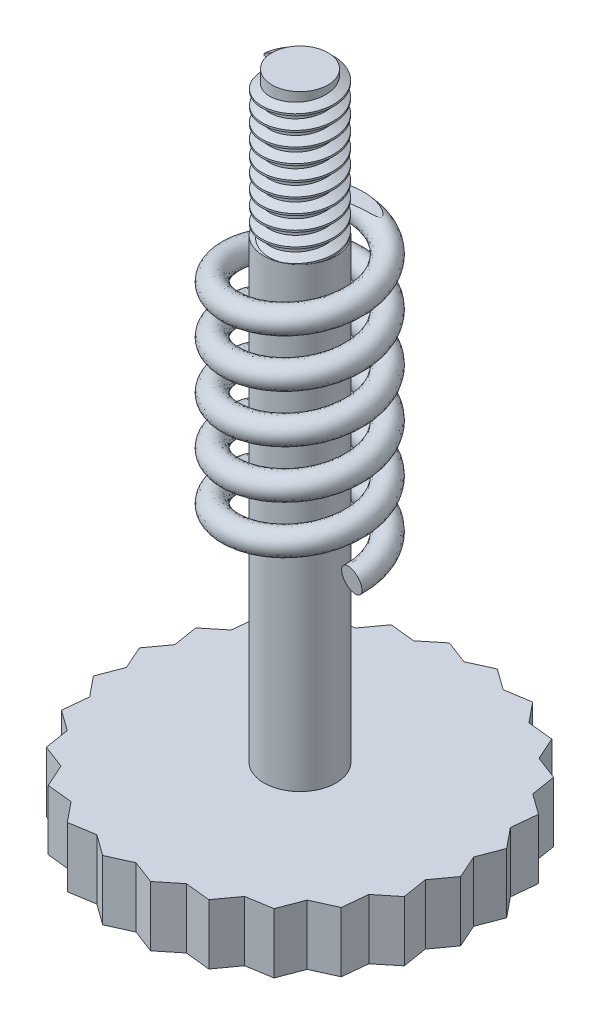
SolidWorks part; units mm, degrees
ref_plane "Front Plane" through (0, 0, 0) normal (0, 0, 1) x (1, 0, 0)
ref_plane "Top Plane" through (0, 0, 0) normal (0, 1, 0) x (1, 0, 0)
ref_plane "Right Plane" through (0, 0, 0) normal (1, 0, 0) x (0, 0, -1)
sketch "Sketch1" plane through (0, 0, 0) normal (0, 1, 0) x (1, 0, 0)
  line L1 (5.821, 4.7381) -> (4.8359, 5.1134)
  line L2 (-1.1928, 7.4102) -> (-2.0103, 6.7447)
  line L3 (-7.0138, 2.6721) -> (-6.8463, 1.6314)
  line L4 (-5.821, -4.7381) -> (-4.8359, -5.1134)
  line L5 (1.1928, -7.4102) -> (2.0103, -6.7447)
  line L6 (7.0138, -2.6721) -> (6.8463, -1.6314)
  line L7 (-7.0304, -0.196) -> (-7.4102, -1.1928)
  line L8 (7.4102, 1.1928) -> (6.7339, 2.0236)
  line L9 (2.6721, 7.0138) -> (1.6145, 6.8435)
  line L10 (-4.7381, 5.821) -> (-5.1194, 4.82)
  line L11 (-7.4102, -1.1928) -> (-6.7339, -2.0236)
  line L12 (-2.6721, -7.0138) -> (-1.6145, -6.8435)
  line L13 (4.7381, -5.821) -> (5.1194, -4.82)
  line L14 (-3.0588, 6.854) -> (-3.685, 5.9905)
  line L15 (-7.4651, 0.778) -> (-7.0304, -0.196)
  line L16 (-4.4063, -6.076) -> (-3.3454, -6.1865)
  line L17 (3.0588, -6.854) -> (3.685, -5.9905)
  line L18 (7.4651, -0.778) -> (7.0304, 0.196)
  line L19 (4.4063, 6.076) -> (3.3454, 6.1865)
  line L20 (6.8402, 3.0895) -> (5.9878, 3.7019)
  line L21 (0.7445, 7.4685) -> (-0.212, 7.0365)
  line L22 (-6.0957, 4.379) -> (-6.1998, 3.3346)
  line L23 (-6.8402, -3.0895) -> (-5.9878, -3.7019)
  line L24 (-0.7445, -7.4685) -> (0.212, -7.0365)
  line L25 (6.0957, -4.379) -> (6.1998, -3.3346)
  line L27 (-6.8463, 1.6314) -> (-7.4651, 0.778)
  line L28 (-6.1998, 3.3346) -> (-7.0138, 2.6721)
  line L29 (-5.1194, 4.82) -> (-6.0957, 4.379)
  line L31 (-3.685, 5.9905) -> (-4.7381, 5.821)
  line L33 (-2.0103, 6.7447) -> (-3.0588, 6.854)
  line L34 (-0.212, 7.0365) -> (-1.1928, 7.4102)
  line L35 (1.6145, 6.8435) -> (0.7445, 7.4685)
  line L36 (-6.7339, -2.0236) -> (-6.8402, -3.0895)
  line L37 (3.3454, 6.1865) -> (2.6721, 7.0138)
  line L38 (4.8359, 5.1134) -> (4.4063, 6.076)
  line L41 (5.9878, 3.7019) -> (5.821, 4.7381)
  line L42 (6.7339, 2.0236) -> (6.8402, 3.0895)
  line L43 (7.0304, 0.196) -> (7.4102, 1.1928)
  line L44 (6.8463, -1.6314) -> (7.4651, -0.778)
  line L45 (6.1998, -3.3346) -> (7.0138, -2.6721)
  line L46 (5.1194, -4.82) -> (6.0957, -4.379)
  line L47 (3.685, -5.9905) -> (4.7381, -5.821)
  line L48 (2.0103, -6.7447) -> (3.0588, -6.854)
  line L49 (0.212, -7.0365) -> (1.1928, -7.4102)
  line L50 (-1.6145, -6.8435) -> (-0.7445, -7.4685)
  line L51 (-3.3454, -6.1865) -> (-2.6721, -7.0138)
  line L52 (-4.8359, -5.1134) -> (-4.4063, -6.076)
  line L55 (-5.9878, -3.7019) -> (-5.821, -4.7381)
  point P1 (0, 0)
extrude "Boss-Extrude1" add sketch "Sketch1" along normal blind 2.5
sketch "Sketch2" plane through (0, 2.5, 0) normal (0, 1, 0) x (1, 0, 0)
  circle A0 centre (0, 0) radius 1.5
  dimension "D1" = 3
extrude "Boss-Extrude2" add sketch "Sketch2" along normal blind 25
sketch "Sketch21" plane through (0, 27.5, 0) normal (0, 1, 0) x (1, 0, 0)
  circle A0 centre (0, 0) radius 1.165
  circle A1 centre (0, 0) radius 1.5
  dimension "D1" = 2.33
  dimension "D2" = 3
extrude "Cut-Extrude1" cut sketch "Sketch21" against normal blind 6
thread "MinColWidth_OnTracking2" pitch 0.6 method extrude profile "HeaderRowsCount4" start angle 0, offset 0, length 6, pitch 0.6, diameter 2.33
ref_plane "Plane4" through (-1.165, 27.5, 0) normal (0, 0, 1) x (-1, 0, 0)
sketch "HeaderRowsCount4" plane through (-1.165, 27.5, 0) normal (0, 0, 1) x (-1, 0, 0)
  line L0 (0, 0) -> (0, 0.6) construction
  line L1 (0, 0) -> (0.3248, 0.1875)
  line L2 (0.3248, 0.1875) -> (0.3248, 0.2625)
  line L3 (0.3248, 0.2625) -> (0, 0.45)
  line L4 (0.3248, 0.225) -> (0, 0.225) construction
  line L11 (0, 0) -> (0, 0.45)
  point P2 (0, 0)
  dimension "Pitch" = 0.6
  dimension "Profile_Angle" = 60
  dimension "Profile_Land" = 0.075
  dimension "Profile_Height" = 0.3248
sketch "Sketch22" plane through (0, 21.5, 0) normal (0, 1, 0) x (1, 0, 0)
  circle A0 centre (0.0352, -0.0449) radius 2.25
  circle A1 centre (0, 0) radius 1.165 construction
  dimension "D1" = 4.5
curve "Helix/Spiral1" pitch 2 height 10.8 radius 2.25 centre (0.0352, 21.5, 0.0449) axis (0, -1, 0) start towards (0, 0, 1)
ref_plane "Plane5" through (2.2575, 10.7, 0.3969) normal (-0.1549, -0.1401, 0.978) x (0.9879, -0.022, 0.1533)
sketch "Sketch23" plane through (2.2575, 10.7, 0.3969) normal (-0.1549, -0.1401, 0.978) x (0.9879, -0.022, 0.1533)
  circle A0 centre (0.3344, -0.118) radius 0.5
  dimension "D1" = 1
sweep "Sweep1" add profiles "Sketch23" path "Helix/Spiral1"
sketch "Sketch24" plane through (0, 21.5, 0) normal (0, 1, 0) x (1, 0, 0)
  circle A0 centre (0, 0) radius 1.5
  circle A1 centre (0.0183, 0) radius 4.9467
extrude "Cut-Extrude2" cut sketch "Sketch24" along normal blind 10
